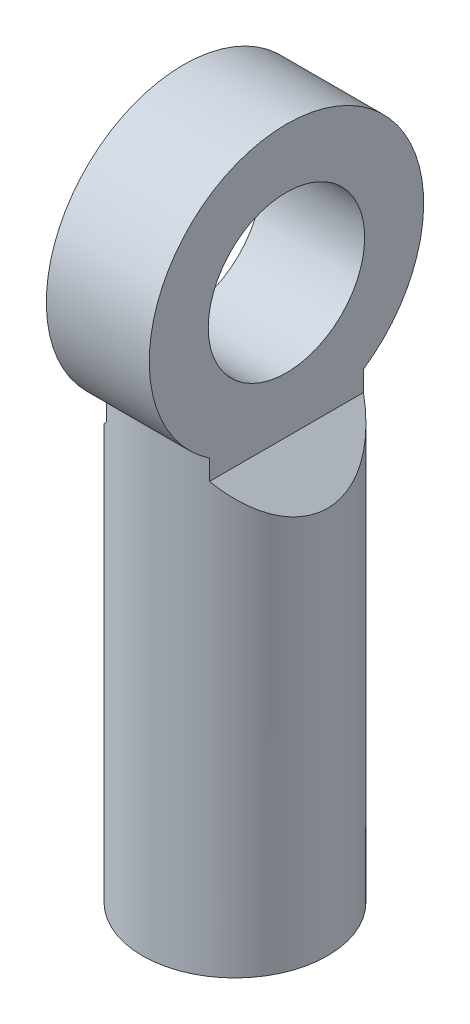
SolidWorks part; units mm, degrees
material "6061-T6 (SS)"
ref_plane "Front Plane" through (0, 0, 0) normal (0, 0, 1) x (1, 0, 0)
ref_plane "Top Plane" through (0, 0, 0) normal (0, 1, 0) x (1, 0, 0)
ref_plane "Right Plane" through (0, 0, 0) normal (1, 0, 0) x (0, 0, -1)
sketch "Sketch1" plane through (0, 0, 0) normal (0, 1, 0) x (1, 0, 0)
  circle A0 centre (0, 0) radius 3.429
  dimension "D1" = 6.858
extrude "Boss-Extrude1" add sketch "Sketch1" along normal blind 24.384
ref_plane "Plane1" through (0, 0, 3.429) normal (0, 0, 1) x (1, 0, 0)
sketch "Sketch2" plane through (0, 0, 3.429) normal (0, 0, 1) x (1, 0, 0)
  line L0 (-1.905, 15.875) -> (-1.905, 24.384)
  line L1 (-1.905, 15.875) -> (-5.334, 12.446)
  line L2 (1.905, 15.875) -> (1.905, 24.384)
  line L3 (1.905, 24.384) -> (-1.905, 24.384) construction
  line L4 (1.905, 15.875) -> (5.334, 12.446)
  line L5 (3.429, 24.384) -> (-3.429, 24.384) construction
  line L6 (0, 0) -> (0, 24.384) construction
  line L7 (-5.334, 12.446) -> (5.334, 12.446) construction
  line L8 (0, 0) -> (0, 12.446) construction
  line L9 (-3.429, 0) -> (3.429, 0) construction
  line L10 (-5.334, 12.446) -> (-5.334, 24.384)
  line L11 (-5.334, 24.384) -> (-1.905, 24.384)
  line L12 (1.905, 24.384) -> (5.334, 24.384)
  line L13 (5.334, 24.384) -> (5.334, 12.446)
  dimension "D1" = 135
  dimension "D2" = 135
  dimension "D3" = 3.81
  dimension "D4" = 12.446
  dimension "D5" = 15.875
extrude "Cut-Extrude1" cut sketch "Sketch2" against normal through all
ref_plane "Plane2" through (0, 0, 0) normal (-1, 0, 0) x (0, 0, 1)
sketch "Sketch3" plane through (0, 0, 0) normal (-1, 0, 0) x (0, 0, 1)
  line L0 (0, 0) -> (0, 20.828) construction
  circle A0 centre (0, 20.828) radius 5.08
  dimension "D1" = 10.16
  dimension "D2" = 20.828
extrude "Boss-Extrude2" add sketch "Sketch3" along normal up to surface and the other way up to surface up to face at (-1.905, 20.1295, 0) other way up to face at (1.905, 20.1295, 0)
hole_wizard "M6x1.0 Tapped Hole1" positions "Sketch4" profile "Sketch6" tap size "M6x1.0" standard "ANSI Metric"
sketch "Sketch4" plane through (0, 0, 0) normal (0, -1, 0) x (-1, 0, 0)
  point P0 (0, 0)
sketch "Sketch6" plane through (0, 0, 0) normal (1, 0, 0) x (0, 0, -1)
  line L0 (0, 0) -> (0, 16.4882)
  line L1 (0, 16.4882) -> (2.5, 14.986)
  line L2 (2.5, 14.986) -> (2.5, 0)
  line L5 (2.5, 0) -> (0, 0)
  line L10 (0, 16.4882) -> (-2.5, 14.986) construction
  line L11 (0, -6.35) -> (0, 107.95) construction
  dimension "Tap Drill Dia." = 5
  dimension "Tap Drill Depth" = 14.986
  dimension "Drill Angle" = 118
hole_wizard "#12 Clearance Hole1" positions "Sketch7" profile "Sketch9" hole size "#12" standard "ANSI Inch" end condition through all
sketch "Sketch7" plane through (-1.905, 0, 0) normal (-1, 0, 0) x (0, 0, 1)
  point P0 (0, 20.828)
sketch "Sketch9" plane through (-1.905, 20.828, 0) normal (0, 1, 0) x (0, 0, 1)
  line L0 (0, 0) -> (0, 5.334)
  line L1 (0, 5.334) -> (2.8956, 5.334)
  line L2 (2.8956, 5.334) -> (2.8956, 0)
  line L5 (2.8956, 0) -> (0, 0)
  line L11 (0, -6.35) -> (0, 107.95) construction
  dimension "Thru Hole Dia." = 5.7912
  dimension "Thru Hole Depth" = 5.334
ref_plane "Plane3" through (0, 25.908, 0) normal (0, 1, 0) x (1, 0, 0)
ref_axis "Axis1" through (1.905, 20.828, 0) along (-1, 0, 0)
ref_point "Point1"
